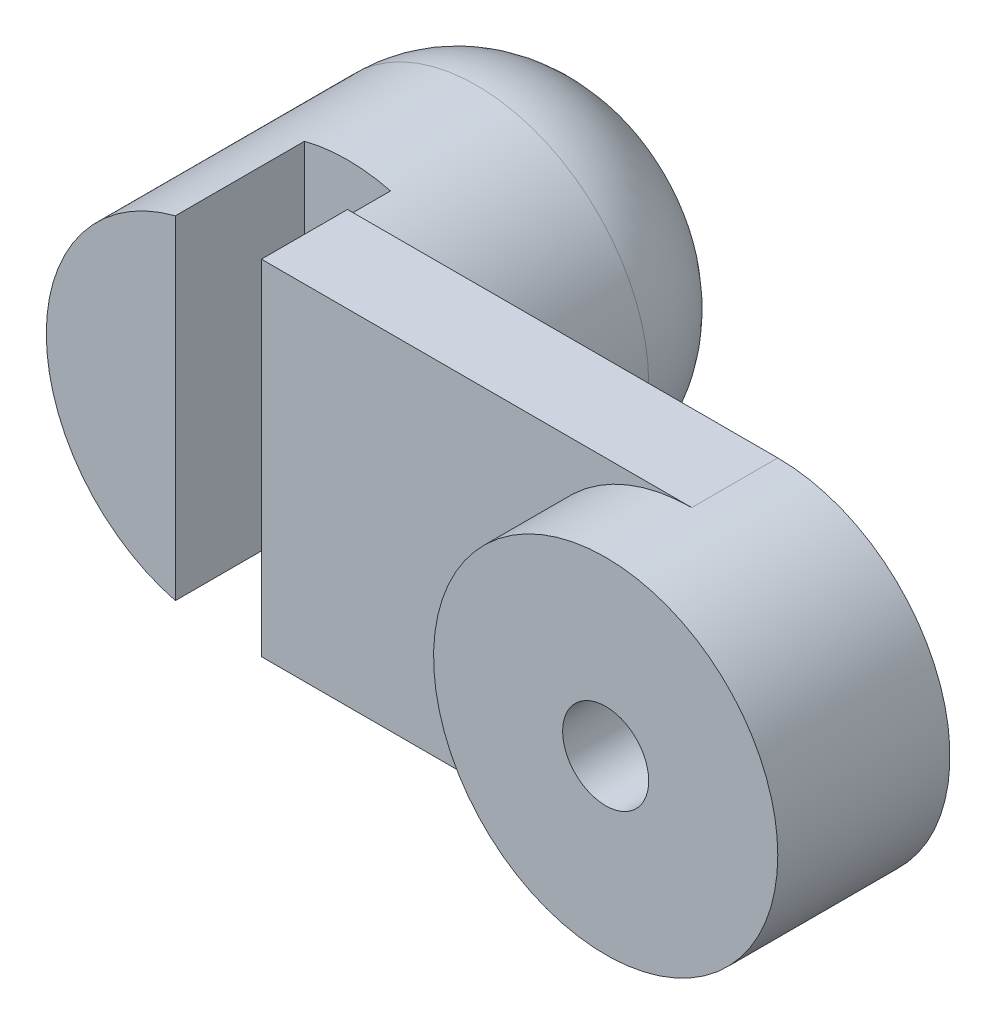
SolidWorks part; units mm, degrees
ref_plane "前视基准面" through (0, 0, 0) normal (0, 0, 1) x (1, 0, 0)
ref_plane "上视基准面" through (0, 0, 0) normal (0, 1, 0) x (1, 0, 0)
ref_plane "右视基准面" through (0, 0, 0) normal (1, 0, 0) x (0, 0, -1)
other "Configuration Table"
sketch "草图1" plane through (0, 0, 0) normal (0, 0, 1) x (1, 0, 0)
  circle A0 centre (0, 0) radius 2
  circle A1 centre (0, 0) radius 0.5
  dimension "D1" = 4
  dimension "D2" = 1
extrude "凸台-拉伸1" add sketch "草图1" along normal blind 4.5
fillet "圆角2" radius 1.5 1 edges at (2, 0, 0)
sketch "草图3" plane through (0, 0, 0) normal (0, 1, 0) x (1, 0, 0)
  line L0 (0, 0) -> (0, -3.5) construction
  line L1 (0, -3.5) -> (0, -4.5)
  line L2 (0, -3.5) -> (5.5, -3.5)
  line L3 (5.5, -3.5) -> (5.5, -4.5)
  line L4 (0, -4.5) -> (5.5, -4.5)
  dimension "D1" = 3.5
  dimension "D2" = 1
  dimension "D3" = 5.5
  dimension "D4" = 1
extrude "凸台-拉伸2" add sketch "草图3" along normal mid plane 4
sketch "草图4" plane through (0, 0, 3.5) normal (0, 0, -1) x (-1, 0, 0)
  line L0 (-5.5, 2) -> (-5.5, -2) construction
  circle A0 centre (-5.5, 0) radius 2
  circle A1 centre (-5.5, 0) radius 0.5
  dimension "D1" = 1
extrude "凸台-拉伸3" add sketch "草图4" against normal blind 1
sketch "草图5" plane through (0, 0, 3.5) normal (0, 0, -1) x (-1, 0, 0)
  line L0 (-5.5, 0.5) -> (-5.5, -0.5) construction
  circle A0 centre (-5.5, 0) radius 0.5
  dimension "D1" = 1
extrude "切除-拉伸2" cut sketch "草图5" against normal blind 4
sketch "草图6" plane through (0, 0, 4.5) normal (0, 0, 1) x (1, 0, 0)
  circle A0 centre (0, 0) radius 0.5
  dimension "D1" = 1
extrude "切除-拉伸3" cut sketch "草图6" against normal through all
sketch "草图2" plane through (0, 0, 4.5) normal (0, 0, 1) x (1, 0, 0)
  line L1 (-0.5, -2.0824) -> (0.5, -2.0824)
  line L2 (-0.5, -2.0824) -> (-0.5, 2.0824)
  line L3 (-0.5, 2.0824) -> (0.5, 2.0824)
  line L4 (0.5, -2.0824) -> (0.5, 2.0824)
  line L5 (-0.5, -2.0824) -> (0.5, 2.0824) construction
  line L6 (-0.5, 2.0824) -> (0.5, -2.0824) construction
  point P0 (0, 0)
  dimension "D1" = 1
extrude "切除-拉伸1" cut sketch "草图2" against normal blind 1.5
sketch "草图7" plane through (0, 0, 4.5) normal (0, 0, 1) x (1, 0, 0)
  circle A0 centre (5.5, 0) radius 0.5
  circle A1 centre (5.5, 0) radius 2
extrude "凸台-拉伸4" add sketch "草图7" along normal blind 1
